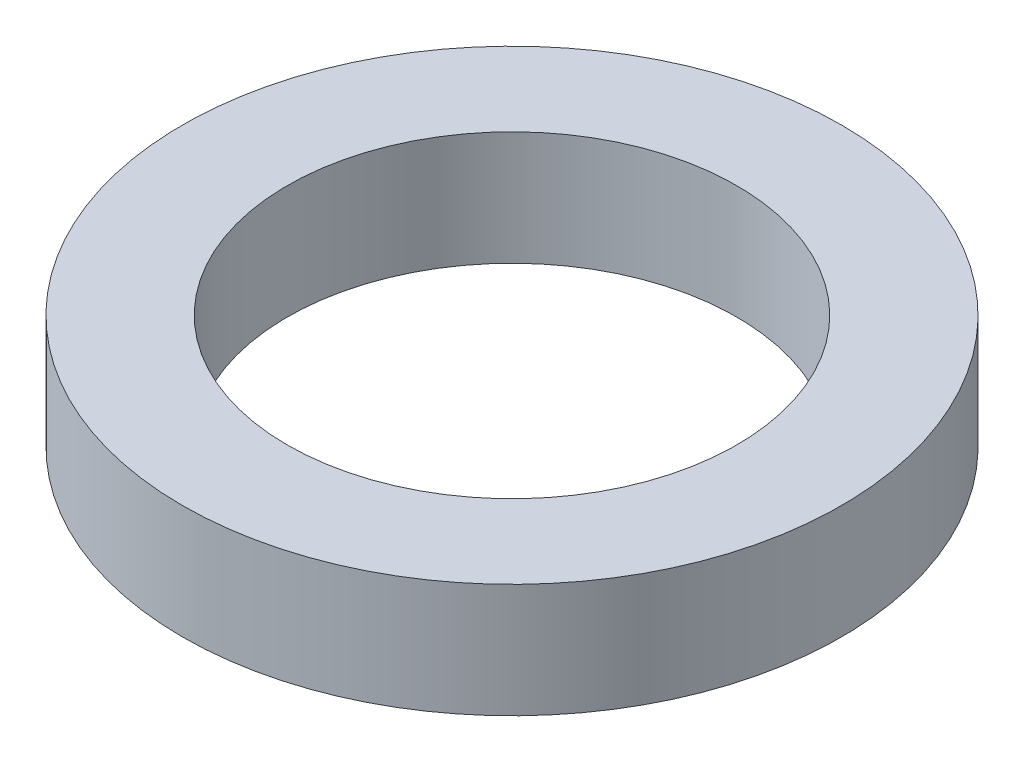
SolidWorks part; units mm, degrees
ref_plane "Front Plane" through (0, 0, 0) normal (0, 0, 1) x (1, 0, 0)
ref_plane "Top Plane" through (0, 0, 0) normal (0, 1, 0) x (1, 0, 0)
ref_plane "Right Plane" through (0, 0, 0) normal (1, 0, 0) x (0, 0, -1)
sketch "Sketch1" plane through (0, 0, 0) normal (0, 1, 0) x (1, 0, 0)
  circle A0 centre (0, 0) radius 55
  dimension "FLANGE_OD" = 110
extrude "Boss-Extrude1" add sketch "Sketch1" along normal blind 19
sketch "Sketch2" plane through (0, 0, 0) normal (0, 1, 0) x (1, 0, 0)
  circle A0 centre (0, 0) radius 37.5
  dimension "BORE_D" = 75
extrude "Cut-Extrude1" cut sketch "Sketch2" along normal through all
sketch "Sketch3" plane through (0, 19, 0) normal (0, 1, 0) x (1, 0, 0)
  circle A0 centre (0, 0) radius 20.998 construction
  circle A1 centre (-20.998, 0) radius 2.3973
  dimension "BOLT_D" = 4.7946
  dimension "BOLT_PCD" = 41.9959
extrude "Cut-Extrude2" cut sketch "Sketch3" against normal blind 14.8628 rebuild error yes
pattern_circular "CirPattern1" count 4 over 360 rebuild error yes
